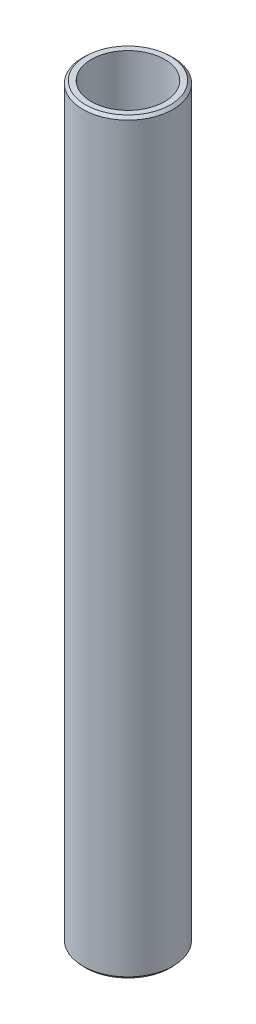
SolidWorks part; units mm, degrees
ref_plane "Front Plane" through (0, 0, 0) normal (0, 0, 1) x (1, 0, 0)
ref_plane "Top Plane" through (0, 0, 0) normal (0, 1, 0) x (1, 0, 0)
ref_plane "Right Plane" through (0, 0, 0) normal (1, 0, 0) x (0, 0, -1)
sketch "Sketch1" plane through (0, 0, 0) normal (0, 1, 0) x (1, 0, 0)
  circle A0 centre (0, 0) radius 22.5
  dimension "SHAFT_OD" = 45
extrude "Boss-Extrude1" add sketch "Sketch1" along normal blind 373.3121
sketch "Sketch2" plane through (0, 0, 0) normal (0, 1, 0) x (1, 0, 0)
  circle A0 centre (0, 0) radius 18.3125
  dimension "BORE_D" = 36.625
extrude "Cut-Extrude1" cut sketch "Sketch2" along normal through all
chamfer "Chamfer1" distance 1.2671 angle 47.71 2 edges at (0, 373.3121, 22.5) (0, 0, 22.5) first distance on face at (0, 373.3121, 22.5) first distance on face at (0, 0, 18.3125)
